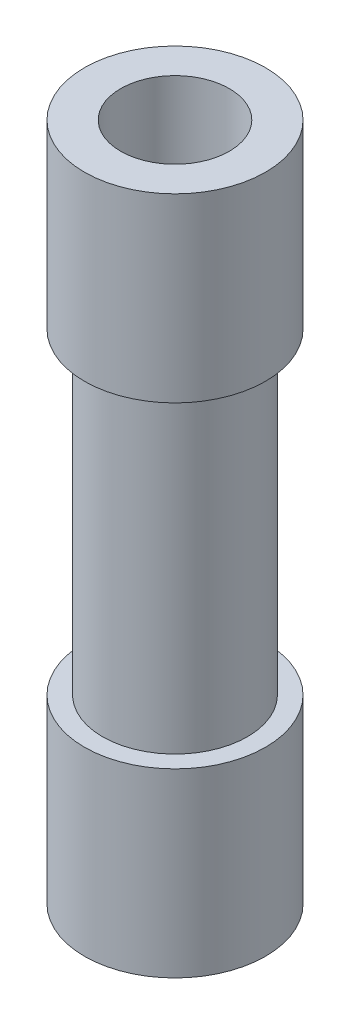
SolidWorks part; units mm, degrees
ref_plane "Front Plane" through (0, 0, 0) normal (0, 0, 1) x (1, 0, 0)
ref_plane "Top Plane" through (0, 0, 0) normal (0, 1, 0) x (1, 0, 0)
ref_plane "Right Plane" through (0, 0, 0) normal (1, 0, 0) x (0, 0, -1)
sketch "Sketch2" plane through (0, 0, 0) normal (0, 1, 0) x (1, 0, 0)
  circle A0 centre (0, 0) radius 1
extrude "Boss-Extrude1" add sketch "Sketch2" along normal blind 7.5
ref_plane "Plane1" through (0, 3.75, 0) normal (0, 1, 0) x (1, 0, 0)
sketch "Sketch4" plane through (0, 3.75, 0) normal (0, 1, 0) x (1, 0, 0)
  circle A0 centre (0, 0) radius 0.8
  dimension "D1" = 1.6
extrude "Cut-Extrude1" cut sketch "Sketch4" against normal blind 1.75 and the other way blind 1.75 flip side to cut
sketch "Sketch5" plane through (0, 7.5, 0) normal (0, 1, 0) x (1, 0, 0)
  circle A0 centre (0, 0) radius 0.6
  dimension "D1" = 1.2
extrude "Cut-Extrude2" cut sketch "Sketch5" against normal blind 7.5
